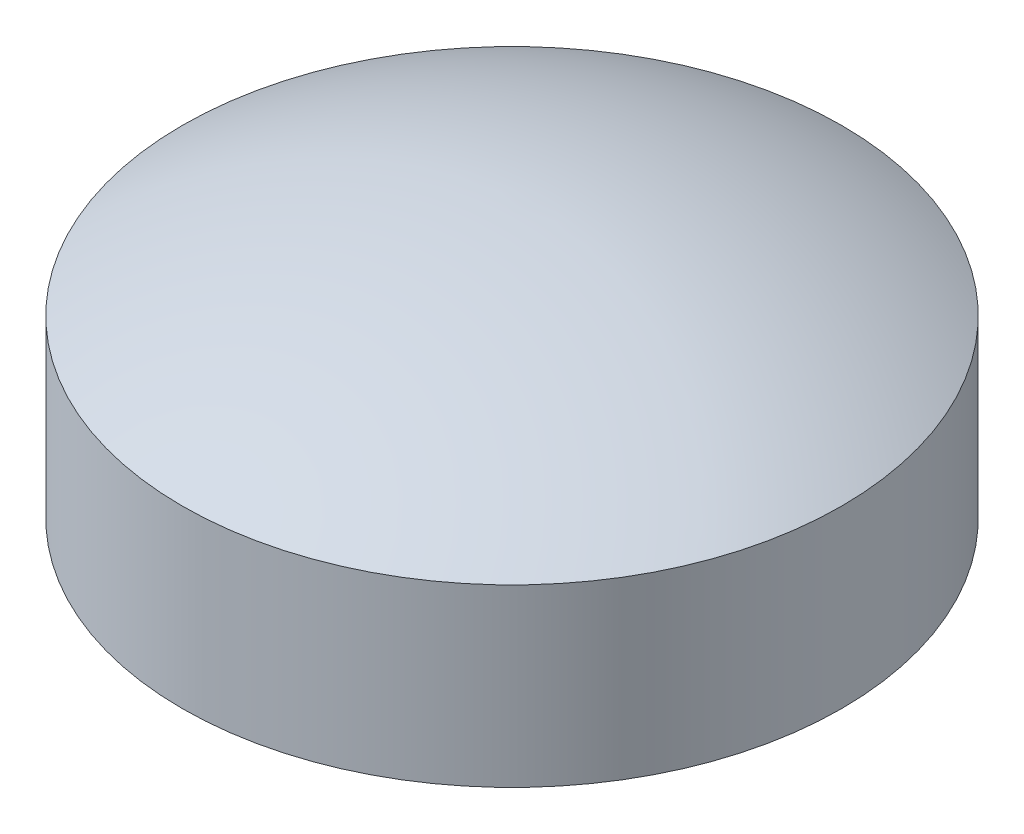
SolidWorks part; units mm, degrees
ref_plane "Front Plane" through (0, 0, 0) normal (0, 0, 1) x (1, 0, 0)
ref_plane "Top Plane" through (0, 0, 0) normal (0, 1, 0) x (1, 0, 0)
ref_plane "Right Plane" through (0, 0, 0) normal (1, 0, 0) x (0, 0, -1)
sketch "Sketch5" plane through (0, 0, 0) normal (0, 0, 1) x (1, 0, 0)
  line L0 (0, -1004.2193) -> (0, 48995.7807) construction
  line L1 (0, 12) -> (0, -48)
  arc A0 (0, 12) -> (0, -48) centre (0, -18) ccw
  point P1 (0, 0)
  point P2 (-8.9526, -13.7807)
  point P7 (0, 0)
  point P9 (0, -18)
  dimension "D1" = 60
  dimension "D2" = 18
revolve "Revolve1" add sketch "Sketch5" angle 360 about L0
sketch "Sketch6" plane through (0, 0, 0) normal (0, 1, 0) x (1, 0, 0)
  circle A0 centre (0, 0) radius 15
  circle A1 centre (0, 0) radius 30
  dimension "D1" = 30
  dimension "D2" = 60
extrude "Cut-Extrude1" cut sketch "Sketch6" against normal through all both and the other way through all
extrude "Cut-Extrude3" cut sketch "Sketch6<5>" against normal up to next contours A0
sketch "Sketch6<5>" plane through (0, 0, 0) normal (0, 1, 0) x (1, 0, 0) same geometry as "Sketch6"
